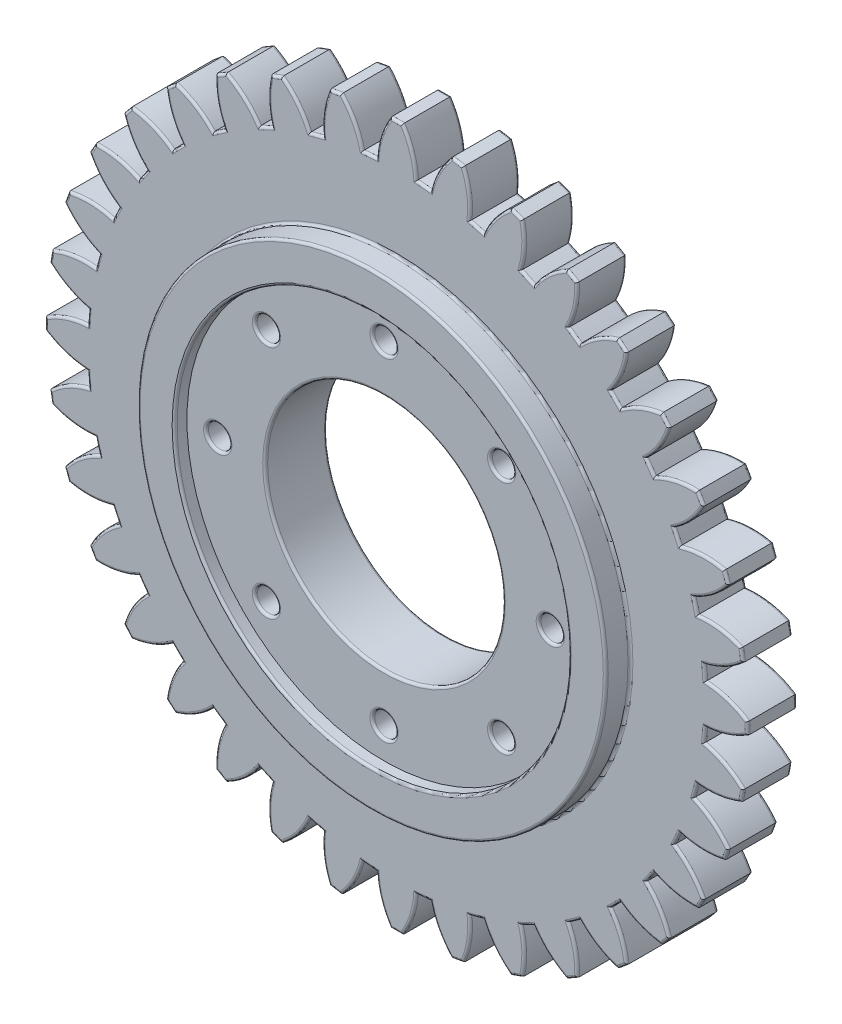
SolidWorks part; units mm, degrees
note: The reader was unsure of these and kept them because the rebuilt part matched: shared geometry of "스케치1<3>".
ref_plane "정면" through (0, 0, 0) normal (0, 0, 1) x (1, 0, 0)
ref_plane "윗면" through (0, 0, 0) normal (0, 1, 0) x (1, 0, 0)
ref_plane "우측면" through (0, 0, 0) normal (1, 0, 0) x (0, 0, -1)
sketch "스케치1" plane through (0, 0, 0) normal (0, 0, 1) x (1, 0, 0)
  line L0 (0, 0) -> (0, 28.5) construction
  line L1 (0, 0) -> (-2.8516, 0) construction
  line L2 (-0.4858, 0) -> (-0.4858, 28.4959) construction
  line L3 (-1.2358, 0) -> (-1.2358, 26.9717) construction
  line L4 (-1.6108, 0) -> (-1.6108, 25.0733) construction
  arc A0 (0.4858, 28.4959) -> (-0.4858, 28.4959) centre (0, 0) ccw
  circle A1 centre (0, 0) radius 27 construction
  circle A2 centre (0, 0) radius 25.125
  spline S0 degree 2 poles (-0.4858, 28.4959) (-1.4984, 26.9368) (-1.6108, 25.0733) knots 0 0 0 1 1 1
  spline S1 degree 2 poles (0.4858, 28.4959) (1.4984, 26.9368) (1.6108, 25.0733) knots 0 0 0 1 1 1
  dimension "D1" = 54
  dimension "D2" = 1.5
  dimension "D3" = 1.875
  dimension "D4" = 0.375
  dimension "D5" = 0.75
  dimension "D6" = 1.2358
extrude "보스-돌출1" add sketch "스케치1" along normal blind 4 contours A2
extrude "보스-돌출2" add sketch "스케치1<3>" along normal blind 4 contours S1 A0 S0 A2
sketch "스케치1<3>" plane through (0, 0, 0) normal (0, 0, 1) x (1, 0, 0) same geometry as "스케치1"
pattern_circular "원형 패턴1" count 36 over 360 about axis through (0, 0, 4) along (0, 0, -1) of "보스-돌출2"
sketch "스케치2" plane through (0, 0, 4) normal (0, 0, 1) x (1, 0, 0)
  circle A0 centre (0, 0) radius 9.65
  dimension "D1" = 19.3
extrude "컷-돌출1" cut sketch "스케치2" against normal blind 10
sketch "스케치4" plane through (0, 0, 4) normal (0, 0, 1) x (1, 0, 0)
  circle A0 centre (0, 0) radius 16
  circle A1 centre (0, 0) radius 9.65
  dimension "D1" = 32
  dimension "D2" = 19.3
extrude "보스-돌출3" add sketch "스케치4" along normal blind 1 contours A0 A1
sketch "스케치5" plane through (0, 0, 5) normal (0, 0, 1) x (1, 0, 0)
  circle A0 centre (13.5, 0) radius 0.95
  circle A1 centre (9.5459, -9.5459) radius 0.95
  circle A2 centre (0, -13.5) radius 0.95
  circle A3 centre (-9.5459, -9.5459) radius 0.95
  circle A4 centre (-13.5, 0) radius 0.95
  circle A5 centre (-9.5459, 9.5459) radius 0.95
  circle A6 centre (0, 13.5) radius 0.95
  circle A7 centre (9.5459, 9.5459) radius 0.95
  point P19 (0, 0)
  dimension "D1" = 1.9
  dimension "D2" = 13.5
  dimension "D3" = 8
extrude "컷-돌출2" cut sketch "스케치5" against normal through all contours A5
sketch "스케치6" plane through (0, 0, 4) normal (0, 0, 1) x (1, 0, 0)
  circle A0 centre (0, 0) radius 16 construction
  circle A1 centre (0, 0) radius 16
  circle A2 centre (0, 0) radius 19
  dimension "D1" = 3
extrude "보스-돌출4" add sketch "스케치6" along normal blind 2 contours A2 A1
fillet "필렛1" radius 0.2 309 edges at (-28.067, 4.949, 0) (-28.067, 4.949, 4) (-25.0294, -2.1898, 0) (-25.0294, -2.1898, 4) (-28.5, 0, 0) (-28.5, 0, 4) (-24.2689, -6.5028, 0) (-24.2689, -6.5028, 4) (-28.067, -4.949, 0) (-28.067, -4.949, 4) (-22.771, -10.6183, 0) (-22.771, -10.6183, 4) (-26.7812, -9.7476, 0) (-26.7812, -9.7476, 4) (-20.5812, -14.4111, 0) (-20.5812, -14.4111, 4) (-24.6817, -14.25, 0) (-24.6817, -14.25, 4) (-17.7661, -17.7661, 0) (-17.7661, -17.7661, 4) (-21.8323, -18.3194, 0) (-21.8323, -18.3194, 4) (-14.4111, -20.5812, 0) (-14.4111, -20.5812, 4) (-18.3194, -21.8323, 0) (-18.3194, -21.8323, 4) (-10.6183, -22.771, 0) (-10.6183, -22.771, 4) (-14.25, -24.6817, 0) (-14.25, -24.6817, 4) (-6.5028, 24.2689, 0) (-6.5028, -24.2689, 0) (-6.5028, -24.2689, 4) (-9.7476, -26.7812, 0) (-9.7476, -26.7812, 4) (-6.5028, 24.2689, 4) (-2.1898, -25.0294, 0) (-2.1898, -25.0294, 4) (-4.949, -28.067, 0) (-4.949, -28.067, 4) (-4.949, 28.067, 0) (2.1898, -25.0294, 0) (2.1898, -25.0294, 4) (0, -28.5, 0) (0, -28.5, 4) (-4.949, 28.067, 4) (6.5028, -24.2689, 0) (6.5028, -24.2689, 4) (4.949, -28.067, 0) (4.949, -28.067, 4) (10.6183, -22.771, 0) (10.6183, -22.771, 4) (9.7476, -26.7812, 0) (9.7476, -26.7812, 4) (14.4111, -20.5812, 0) (14.4111, -20.5812, 4) (14.25, -24.6817, 0) (14.25, -24.6817, 4) (17.7661, -17.7661, 0) (17.7661, -17.7661, 4) (18.3194, -21.8323, 0) (18.3194, -21.8323, 4) (20.5812, -14.4111, 0) (20.5812, -14.4111, 4) (21.8323, -18.3194, 0) (21.8323, -18.3194, 4) (22.771, -10.6183, 0) (22.771, -10.6183, 4) (24.6817, -14.25, 0) (24.6817, -14.25, 4) (24.2689, -6.5028, 0) (24.2689, -6.5028, 4) (26.7812, -9.7476, 0) (26.7812, -9.7476, 4) (25.0294, -2.1898, 0) (25.0294, -2.1898, 4) (-10.6183, 22.771, 0) (28.067, -4.949, 0) (28.067, -4.949, 4) (-10.6183, 22.771, 4) (25.0294, 2.1898, 0) (25.0294, 2.1898, 4) (28.5, 0, 0) (28.5, 0, 4) (24.2689, 6.5028, 0) (24.2689, 6.5028, 4) (-9.7476, 26.7812, 0) (28.067, 4.949, 0) (28.067, 4.949, 4) (22.771, 10.6183, 0) (22.771, 10.6183, 4) (-9.7476, 26.7812, 4) (26.7812, 9.7476, 0) (26.7812, 9.7476, 4) (20.5812, 14.4111, 0) (20.5812, 14.4111, 4) (24.6817, 14.25, 0) (24.6817, 14.25, 4) (17.7661, 17.7661, 0) (17.7661, 17.7661, 4) (21.8323, 18.3194, 0) (21.8323, 18.3194, 4) (14.4111, 20.5812, 0) (14.4111, 20.5812, 4) (18.3194, 21.8323, 0) (18.3194, 21.8323, 4) (10.6183, 22.771, 0) (10.6183, 22.771, 4) (14.25, 24.6817, 0) (14.25, 24.6817, 4) (6.5028, 24.2689, 0) (6.5028, 24.2689, 4) (9.7476, 26.7812, 0) (9.7476, 26.7812, 4) (2.1898, 25.0294, 0) (2.1898, 25.0294, 4) (4.949, 28.067, 0) (4.949, 28.067, 4) (-14.4111, 20.5812, 0) (-14.4111, 20.5812, 4) (-14.25, 24.6817, 0) (-14.25, 24.6817, 4) (9.65, 0, 0) (9.65, 0, 5) (14.45, 0, 0) (14.45, 0, 5) (10.4959, -9.5459, 0) (10.4959, -9.5459, 5) (0.95, -13.5, 0) (0.95, -13.5, 5) (-8.5959, -9.5459, 0) (-8.5959, -9.5459, 5) (-12.55, 0, 0) (-12.55, 0, 5) (-8.5959, 9.5459, 0) (-8.5959, 9.5459, 5) (0.95, 13.5, 0) (0.95, 13.5, 5) (10.4959, 9.5459, 0) (10.4959, 9.5459, 5) (-17.7661, 17.7661, 0) (-17.7661, 17.7661, 4) (16, 0, 6) (19, 0, 4) (19, 0, 6) (-18.3194, 21.8323, 0) (-2.1898, 25.0294, 0) (-18.3194, 21.8323, 4) (-2.1898, 25.0294, 4) (-20.5812, 14.4111, 0) (-20.5812, 14.4111, 4) (-21.8323, 18.3194, 0) (-21.8323, 18.3194, 4) (0, 28.5, 0) (-22.771, 10.6183, 0) (-22.771, 10.6183, 4) (-24.6817, 14.25, 0) (-24.6817, 14.25, 4) (-24.2689, 6.5028, 0) (0, 28.5, 4) (-24.2689, 6.5028, 4) (-26.7812, 9.7476, 0) (-26.7812, 9.7476, 4) (-25.0294, 2.1898, 0) (-25.0294, 2.1898, 4)
